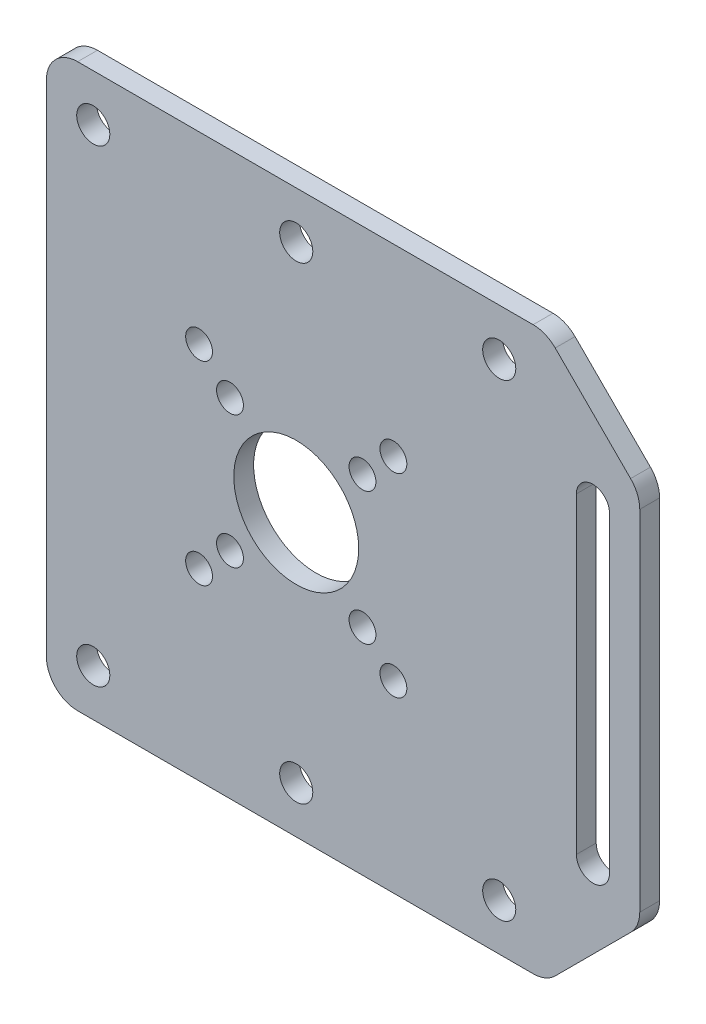
SolidWorks part; units mm, degrees
material "5052-H32"
ref_plane "Front Plane" through (0, 0, 0) normal (0, 0, 1) x (1, 0, 0)
ref_plane "Top Plane" through (0, 0, 0) normal (0, 1, 0) x (1, 0, 0)
ref_plane "Right Plane" through (0, 0, 0) normal (1, 0, 0) x (0, 0, -1)
sketch "Sketch1" plane through (0, 0, 0) normal (0, 0, 1) x (1, 0, 0)
  line L0 (0, 0) -> (-15.5563, 15.5563) construction
  line L1 (0, 0) -> (-31.5, 0) construction
  line L2 (40, 45) -> (55, 30)
  line L3 (-40, 45) -> (40, 45)
  line L4 (-40, 45) -> (-40, -45)
  line L5 (-40, -45) -> (40, -45)
  line L7 (32.5, 37.5) -> (-32.5, 37.5) construction
  line L8 (32.5, 37.5) -> (32.5, -37.5) construction
  line L9 (32.5, -37.5) -> (-32.5, -37.5) construction
  line L10 (-32.5, 37.5) -> (-32.5, -37.5) construction
  line L11 (55, 30) -> (55, -30)
  line L12 (55, -30) -> (40, -45)
  line L13 (44.85, 25) -> (44.85, -25)
  line L14 (50.15, 25) -> (50.15, -25)
  line L15 (40, 0) -> (55, 0) construction
  circle A0 centre (0, 0) radius 15 construction
  circle A1 centre (0, 0) radius 22 construction
  circle A2 centre (0, 0) radius 10
  circle A3 centre (-10.6066, 10.6066) radius 2 construction
  circle A5 centre (-15.5563, 15.5563) radius 2 construction
  circle A11 centre (0, 0) radius 31.5 construction
  circle A14 centre (15.5563, 15.5563) radius 2 construction
  circle A15 centre (10.6066, 10.6066) radius 2 construction
  circle A16 centre (15.5563, -15.5563) radius 2 construction
  circle A17 centre (10.6066, -10.6066) radius 2 construction
  circle A18 centre (-15.5563, -15.5563) radius 2 construction
  circle A19 centre (-10.6066, -10.6066) radius 2 construction
  circle A20 centre (32.5, 37.5) radius 2.5 construction
  circle A21 centre (-32.5, 37.5) radius 2.5 construction
  circle A22 centre (-32.5, -37.5) radius 2.5 construction
  circle A23 centre (32.5, -37.5) radius 2.5 construction
  circle A24 centre (0, 37.5) radius 2.5 construction
  circle A25 centre (0, -37.5) radius 2.5 construction
  arc A26 (44.85, 25) -> (50.15, 25) centre (47.5, 25) cw
  arc A27 (50.15, -25) -> (44.85, -25) centre (47.5, -25) cw
  point P8 (0, 45)
  point P11 (-40, 0)
  point P17 (0, 0)
  point P27 (0, 0)
  point P32 (0, 0)
  point P40 (0, 0)
  point P41 (0, 37.5)
  point P46 (0, 0)
  point P49 (31.5, 0)
  point P50 (55, 0)
  point P58 (49.7786, 18.5067)
  point P59 (50.15, 0)
  point P61 (0, 0)
  point P62 (47.5, 0)
  point P63 (50.8722, 20.2839)
  point P64 (57.776, 21.3776)
  point P65 (40, -38.706)
  point P66 (40, 44.5497)
  point P67 (40, 45)
  point P68 (40, 45)
  point P69 (56.3063, 30)
  point P70 (43.25, 25)
  point P71 (36.9586, 0)
  point P72 (32.5, 41.0084)
  point P73 (32.5, 0)
  dimension "D1" = 4
  dimension "D2" = 63
  dimension "D4" = 20
  dimension "D5" = 30
  dimension "D6" = 44
  dimension "D10" = 5
  dimension "D14" = 2.65
  dimension "D3" = 80
  dimension "D7" = 45
  dimension "D9" = 90
  dimension "D11" = 65
  dimension "D12" = 75
  dimension "D13" = 15
  dimension "D15" = 50
  dimension "D16" = 60
  dimension "D8" = 4
base flange "Base-Flange1" sketch "Sketch1" thickness 3.175 reverse thickness direction no parameters "D1"=0.7366
hole_wizard "M4 Clearance Hole1" positions "3DSketch2" profile "Sketch7" hole size "M4" standard "ANSI Metric" end condition up to next
sketch3d "3DSketch2"
  circle A0 centre (0, 0, 0) radius 15 construction
  point P0 (-15.5563, 15.5563, 0)
  point P2 (15.5563, 15.5563, 0)
  point P4 (10.6066, 10.6066, 0)
  point P6 (-10.6066, 10.6066, 0)
  point P8 (-15.5563, -15.5563, 0)
  point P10 (15.5563, -15.5563, 0)
  point P12 (10.6066, -10.6066, 0)
  point P14 (-10.6066, -10.6066, 0)
  point P24 (0, 0, 15)
sketch "Sketch7" plane through (-15.5563, 15.5563, 0) normal (1, 0, 0) x (0, -1, 0)
  line L0 (0, 0) -> (0, 3.175)
  line L1 (0, 3.175) -> (2.15, 3.175)
  line L2 (2.15, 3.175) -> (2.15, 0)
  line L5 (2.15, 0) -> (0, 0)
  line L11 (0, -6.35) -> (0, 107.95) construction
  dimension "Thru Hole Dia." = 4.3
  dimension "Thru Hole Depth" = 3.175
hole_wizard "M5 Clearance Hole1" positions "3DSketch3" profile "Sketch8" hole size "M5" standard "ANSI Metric" end condition up to next
sketch3d "3DSketch3"
  point P0 (-32.5, 37.5, 0)
  point P2 (32.5, 37.5, 0)
  point P4 (32.5, -37.5, 0)
  point P6 (-32.5, -37.5, 0)
  point P17 (0, 37.5, 0)
  point P19 (0, -37.5, 0)
  point P22 (0, -32.5, 0)
  point P24 (0, 32.5, 0)
sketch "Sketch8" plane through (-32.5, 37.5, 0) normal (1, 0, 0) x (0, -1, 0)
  line L0 (0, 0) -> (0, 3.175)
  line L1 (0, 3.175) -> (2.65, 3.175)
  line L2 (2.65, 3.175) -> (2.65, 0)
  line L5 (2.65, 0) -> (0, 0)
  line L11 (0, -6.35) -> (0, 107.95) construction
  dimension "Thru Hole Dia." = 5.3
  dimension "Thru Hole Depth" = 3.175
fillet "Fillet1" radius 5 6 edges at (-40, -45, -1.5875) (-40, 45, -1.5875) (40, -45, -1.5875) (55, -30, -1.5875) (55, 30, -1.5875) (40, 45, -1.5875)
sketch "Bend-Lines1" [suppressed] plane through (0, 0, 0) normal (0, 1, 0) x (1, 0, 0)
sketch "Bounding-Box1" [suppressed] plane through (0, 0, 0) normal (0, 1, 0) x (1, 0, 0)
sheet metal parameters "Sheet-Metal1" thickness 3.175 parameters "D1"=0.7366
flat pattern "Flat-Pattern1" [suppressed]
sketch "Bend-Lines2" plane through (0, 0, 0) normal (0, 1, 0) x (1, 0, 0)
sketch3d "Bounding-Box2" [suppressed]
  line L0 (-40, 50, 0) -> (-40, -50, 0) construction
  line L1 (40, 50, 0) -> (40, -50, 0) construction
  line L2 (-40, 50, 0) -> (40, 50, 0) construction
  line L3 (-40, -50, 0) -> (40, -50, 0) construction
sheet metal parameters "Sheet-Metal2" thickness 3.175 parameters "D1"=0.7366
flat pattern "Flat-Pattern1"
sketch "Bend-Lines2" plane through (0, 0, 0) normal (0, 1, 0) x (1, 0, 0)
sketch3d "Bounding-Box2" [suppressed]
  line L0 (40, 50, 0) -> (40, -50, 0) construction
  line L1 (-40, 50, 0) -> (-40, -50, 0) construction
  line L2 (40, 50, 0) -> (-40, 50, 0) construction
  line L3 (40, -50, 0) -> (-40, -50, 0) construction
sheet metal parameters "Sheet-Metal3" thickness 3.175 parameters "D1"=0.7366
flat pattern "Flat-Pattern1" [suppressed]
sketch "Bend-Lines2" plane through (0, 0, 0) normal (0, 1, 0) x (1, 0, 0)
sketch3d "Bounding-Box2" [suppressed]
  line L0 (-40, 45, 0) -> (55, 45, 0) construction
  line L1 (-40, -45, 0) -> (55, -45, 0) construction
  line L2 (-40, 45, 0) -> (-40, -45, 0) construction
  line L3 (55, 45, 0) -> (55, -45, 0) construction
